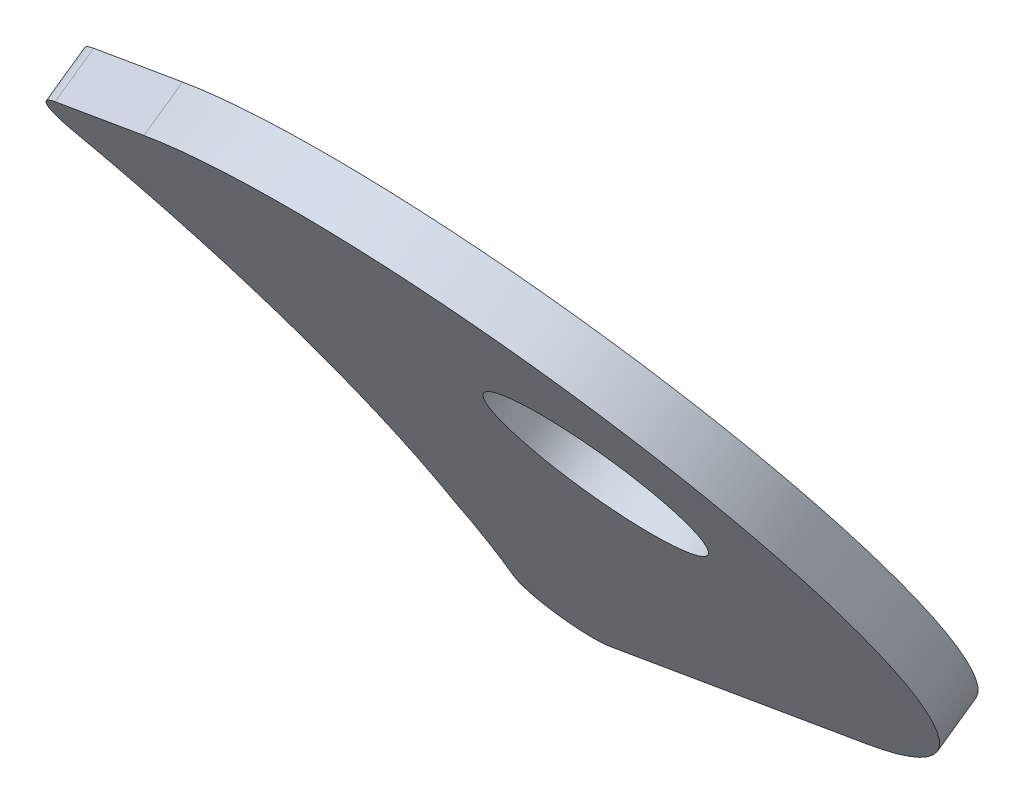
SolidWorks part; units mm, degrees
ref_plane "Front Plane" through (0, 0, 0) normal (0, 0, 1) x (1, 0, 0)
ref_plane "Top Plane" through (0, 0, 0) normal (0, 1, 0) x (1, 0, 0)
ref_plane "Right Plane" through (0, 0, 0) normal (1, 0, 0) x (0, 0, -1)
ref_plane "Plane1" through (0, 229.6997, -328.0452) normal (0, -0.5736, 0.8192) x (1, 0, 0)
sketch "Sketch1" plane through (0, 229.6997, -328.0452) normal (0, -0.5736, 0.8192) x (1, 0, 0)
  line L0 (356.2999, 70.5516) -> (376.9254, 80.822)
  line L1 (365.6036, 103.5591) -> (344.9781, 93.2888)
  line L2 (344.9781, 93.2888) -> (356.2999, 70.5516)
  line L3 (371.2645, 92.1906) -> (375.5277, 94.3134) construction
  arc A0 (376.9254, 80.822) -> (365.6036, 103.5591) centre (371.2645, 92.1906) ccw
  circle A1 centre (375.5277, 94.3134) radius 3.302
  point P4 (350.639, 81.9202)
  dimension "D1" = 4.7625
  dimension "D2" = 25.4
extrude "Boss-Extrude1" add sketch "Sketch1" along normal blind 1.5875
ref_plane "Plane2" through (364.3517, 343.6254, -135.3997) normal (-0.0893, -0.3048, -0.9482) x (-0.996, 0.0273, 0.085)
sketch "Sketch2" plane through (364.3517, 343.6254, -135.3997) normal (-0.0893, -0.3048, -0.9482) x (-0.996, 0.0273, 0.085)
  circle A0 centre (0, 0) radius 12.7
  dimension "D1" = 25.4
extrude "Cut-Extrude1" cut sketch "Sketch2" along normal through all
sketch "Sketch3" plane through (0, 228.7892, -326.7448) normal (0, -0.5736, 0.8192) x (1, 0, 0)
  line L0 (359.8287, 100.6835) -> (358.4382, 99.9911)
  line L1 (358.4382, 99.9911) -> (360.8703, 72.8274)
  ellipse E0 centre (350.8744, 84.0131) end of major axis (353.2331, 104.9802) minor radius 12.7 (360.8703, 72.8274) -> (359.8287, 100.6835) ccw construction
  ellipse E1 centre (350.8744, 84.0131) end of major axis (353.2331, 104.9802) minor radius 12.7 (360.8703, 72.8274) -> (359.8287, 100.6835) ccw
extrude "Cut-Extrude2" cut sketch "Sketch3" against normal through all
sketch "Sketch4" plane through (0, 229.6997, -328.0452) normal (0, 0.5736, -0.8192) x (-1, 0, 0)
  line L0 (-361.6175, 73.1995) -> (-360.8703, 72.8274)
  line L1 (-360.8703, 72.8274) -> (-363.3614, 81.5487)
  ellipse E0 centre (-350.639, 81.9202) end of major axis (-352.9976, 102.8873) minor radius 12.7 (-363.3614, 81.5487) -> (-361.6175, 73.1995) ccw construction
  ellipse E1 centre (-350.639, 81.9202) end of major axis (-352.9976, 102.8873) minor radius 12.7 (-363.3614, 81.5487) -> (-361.6175, 73.1995) ccw
extrude "Cut-Extrude3" cut sketch "Sketch4" against normal through all
fillet "Fillet1" radius 1.5875 2 edges at (359.8287, 311.7196, -269.6453) (361.6175, 289.206, -285.4095)
